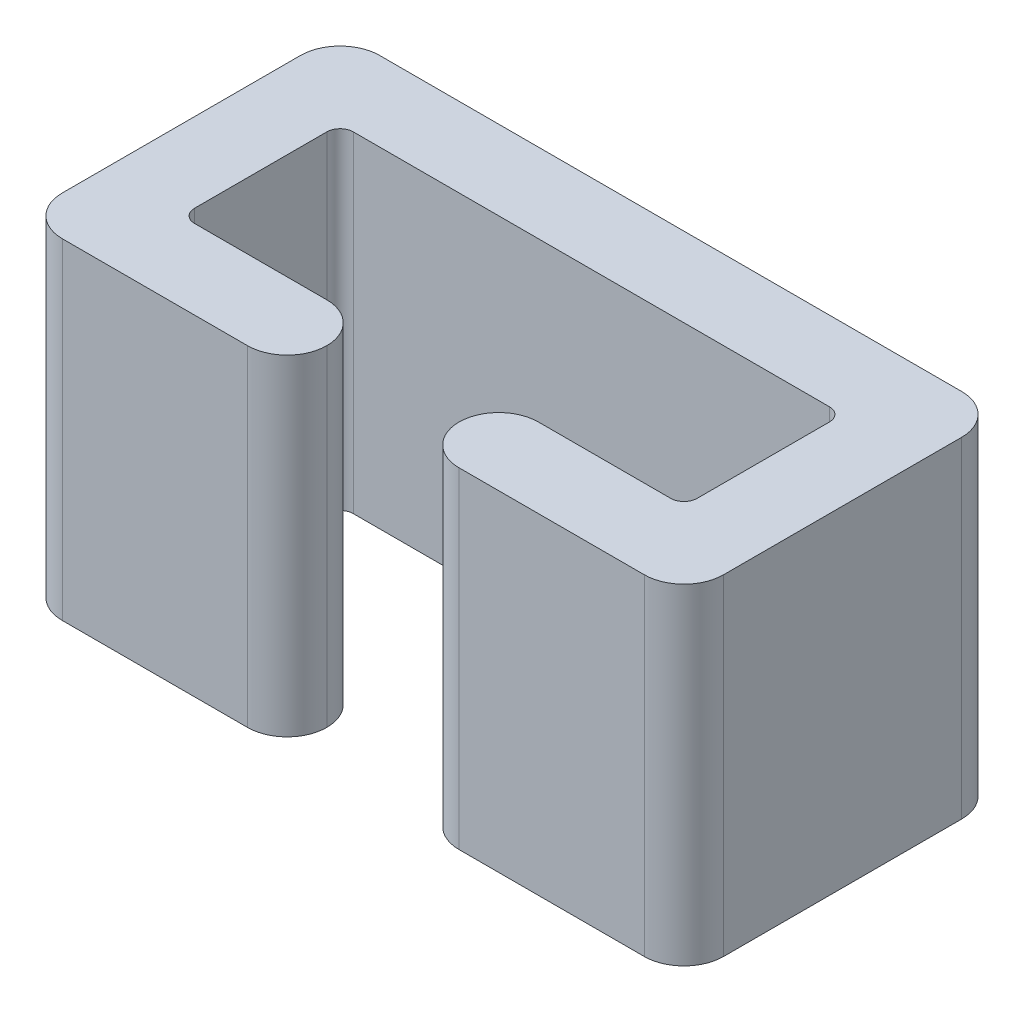
SolidWorks part; units mm, degrees
material "ABS"
ref_plane "Front Plane" through (0, 0, 0) normal (0, 0, 1) x (1, 0, 0)
ref_plane "Top Plane" through (0, 0, 0) normal (0, 1, 0) x (1, 0, 0)
ref_plane "Right Plane" through (0, 0, 0) normal (1, 0, 0) x (0, 0, -1)
sketch "Sketch1" plane through (0, 0, 0) normal (0, 1, 0) x (1, 0, 0)
  line L0 (-5, 0) -> (5, 0)
  line L1 (-5, 0) -> (-5, -4.8)
  line L2 (-5, -4.8) -> (-1, -4.8)
  line L3 (-1, -4.8) -> (-1, -3.6)
  line L4 (-1, -3.6) -> (-3.8, -3.6)
  line L5 (-3.8, -3.6) -> (-3.8, -1.2)
  line L6 (-3.8, -1.2) -> (3.8, -1.2)
  line L7 (3.8, -1.2) -> (3.8, -3.6)
  line L8 (3.8, -3.6) -> (1, -3.6)
  line L9 (1, -3.6) -> (1, -4.8)
  line L10 (1, -4.8) -> (5, -4.8)
  line L11 (5, -4.8) -> (5, 0)
  point P4 (0, 0)
  dimension "D1" = 10
  dimension "D2" = 1.2
  dimension "D3" = 2.4
  dimension "D4" = 1.2
  dimension "D5" = 1.2
  dimension "D6" = 2
extrude "Boss-Extrude1" add sketch "Sketch1" along normal blind 5
fillet "Fillet1" radius 0.6 8 edges at (-5, 2.5, 0) (5, 2.5, 0) (5, 2.5, 4.8) (1, 2.5, 4.8) (1, 2.5, 3.6) (-1, 2.5, 3.6) (-1, 2.5, 4.8) (-5, 2.5, 4.8)
fillet "Fillet2" radius 0.2 4 edges at (-3.8, 2.5, 3.6) (3.8, 2.5, 1.2) (3.8, 2.5, 3.6) (-3.8, 2.5, 1.2)
